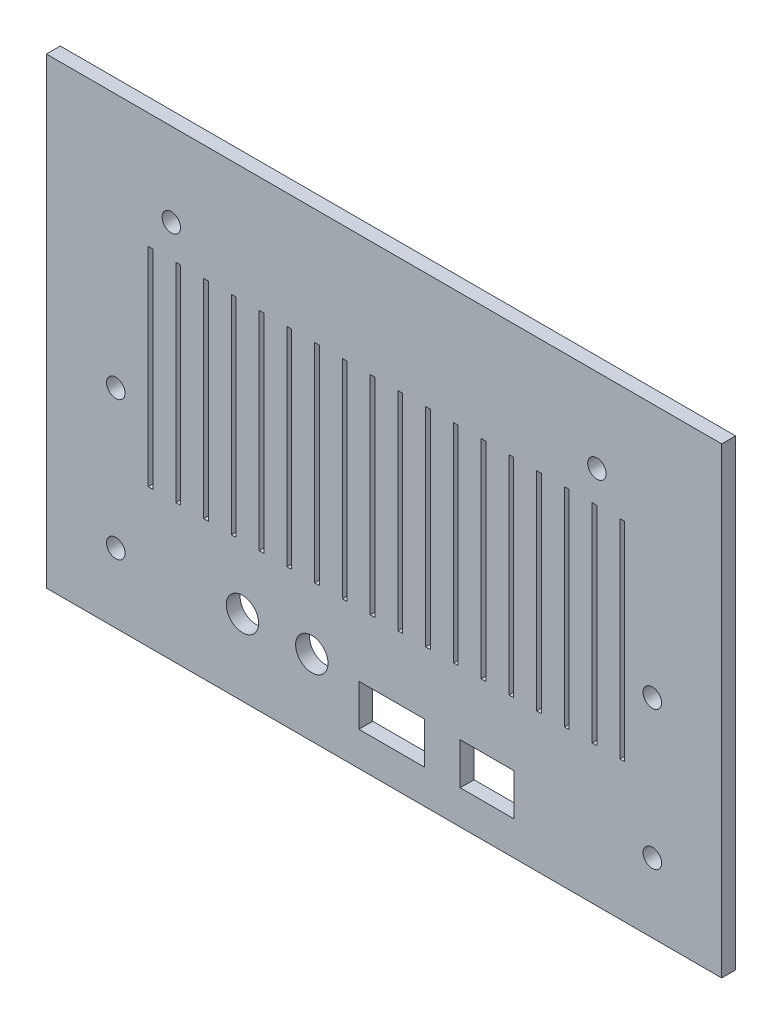
SolidWorks part; units mm, degrees
ref_plane "Front Plane" through (0, 0, 0) normal (0, 0, 1) x (1, 0, 0)
ref_plane "Top Plane" through (0, 0, 0) normal (0, 1, 0) x (1, 0, 0)
ref_plane "Right Plane" through (0, 0, 0) normal (1, 0, 0) x (0, 0, -1)
sketch "Sketch1" plane through (0, 0, 0) normal (0, 0, 1) x (1, 0, 0)
  line L1 (-48.2442, 79.6334) -> (97.7558, 79.6334)
  line L2 (-48.2442, 79.6334) -> (-48.2442, -20.3666)
  line L3 (-48.2442, -20.3666) -> (97.7558, -20.3666)
  line L4 (97.7558, 79.6334) -> (97.7558, -20.3666)
  dimension "D1" = 146
  dimension "D2" = 100
extrude "Boss-Extrude1" add sketch "Sketch1" along normal blind 3
sketch "Sketch2" plane through (0, 0, 3) normal (0, 0, 1) x (1, 0, 0)
  line L0 (-20.2442, 54.6334) -> (-19.2442, 54.6334)
  line L1 (-26.2442, 54.6334) -> (-25.2442, 54.6334)
  line L2 (-26.2442, 54.6334) -> (-26.2442, 9.6334)
  line L3 (-26.2442, 9.6334) -> (-25.2442, 9.6334)
  line L4 (-25.2442, 54.6334) -> (-25.2442, 9.6334)
  line L5 (-20.2442, 54.6334) -> (-20.2442, 9.6334)
  line L6 (-20.2442, 9.6334) -> (-19.2442, 9.6334)
  line L7 (-19.2442, 54.6334) -> (-19.2442, 9.6334)
  line L8 (-14.2442, 54.6334) -> (-13.2442, 54.6334)
  line L9 (-14.2442, 54.6334) -> (-14.2442, 9.6334)
  line L10 (-14.2442, 9.6334) -> (-13.2442, 9.6334)
  line L11 (-13.2442, 54.6334) -> (-13.2442, 9.6334)
  line L12 (-8.2442, 54.6334) -> (-7.2442, 54.6334)
  line L13 (-8.2442, 54.6334) -> (-8.2442, 9.6334)
  line L14 (-8.2442, 9.6334) -> (-7.2442, 9.6334)
  line L15 (-7.2442, 54.6334) -> (-7.2442, 9.6334)
  line L16 (-2.2442, 54.6334) -> (-1.2442, 54.6334)
  line L17 (-2.2442, 54.6334) -> (-2.2442, 9.6334)
  line L18 (-2.2442, 9.6334) -> (-1.2442, 9.6334)
  line L19 (-1.2442, 54.6334) -> (-1.2442, 9.6334)
  line L20 (3.7558, 54.6334) -> (4.7558, 54.6334)
  line L21 (3.7558, 54.6334) -> (3.7558, 9.6334)
  line L22 (3.7558, 9.6334) -> (4.7558, 9.6334)
  line L23 (4.7558, 54.6334) -> (4.7558, 9.6334)
  line L24 (-48.2442, 79.6334) -> (-48.2442, -20.3666) construction
  line L25 (-48.2442, -20.3666) -> (97.7558, -20.3666) construction
  line L26 (9.7558, 54.6334) -> (10.7558, 54.6334)
  line L27 (9.7558, 54.6334) -> (9.7558, 9.6334)
  line L28 (9.7558, 9.6334) -> (10.7558, 9.6334)
  line L29 (10.7558, 54.6334) -> (10.7558, 9.6334)
  line L30 (15.7558, 54.6334) -> (16.7558, 54.6334)
  line L31 (15.7558, 54.6334) -> (15.7558, 9.6334)
  line L32 (15.7558, 9.6334) -> (16.7558, 9.6334)
  line L33 (16.7558, 54.6334) -> (16.7558, 9.6334)
  line L34 (21.7558, 54.6334) -> (22.7558, 54.6334)
  line L35 (21.7558, 54.6334) -> (21.7558, 9.6334)
  line L36 (21.7558, 9.6334) -> (22.7558, 9.6334)
  line L37 (22.7558, 54.6334) -> (22.7558, 9.6334)
  line L38 (33.7558, 54.6334) -> (34.7558, 54.6334)
  line L39 (27.7558, 54.6334) -> (28.7558, 54.6334)
  line L40 (27.7558, 54.6334) -> (27.7558, 9.6334)
  line L41 (27.7558, 9.6334) -> (28.7558, 9.6334)
  line L42 (28.7558, 54.6334) -> (28.7558, 9.6334)
  line L43 (33.7558, 54.6334) -> (33.7558, 9.6334)
  line L44 (33.7558, 9.6334) -> (34.7558, 9.6334)
  line L45 (34.7558, 54.6334) -> (34.7558, 9.6334)
  line L46 (39.7558, 54.6334) -> (40.7558, 54.6334)
  line L47 (39.7558, 54.6334) -> (39.7558, 9.6334)
  line L48 (39.7558, 9.6334) -> (40.7558, 9.6334)
  line L49 (40.7558, 54.6334) -> (40.7558, 9.6334)
  line L50 (45.7558, 54.6334) -> (46.7558, 54.6334)
  line L51 (45.7558, 54.6334) -> (45.7558, 9.6334)
  line L52 (45.7558, 9.6334) -> (46.7558, 9.6334)
  line L53 (46.7558, 54.6334) -> (46.7558, 9.6334)
  line L54 (51.7558, 54.6334) -> (52.7558, 54.6334)
  line L55 (51.7558, 54.6334) -> (51.7558, 9.6334)
  line L56 (51.7558, 9.6334) -> (52.7558, 9.6334)
  line L57 (52.7558, 54.6334) -> (52.7558, 9.6334)
  line L58 (57.7558, 54.6334) -> (58.7558, 54.6334)
  line L59 (57.7558, 54.6334) -> (57.7558, 9.6334)
  line L60 (57.7558, 9.6334) -> (58.7558, 9.6334)
  line L61 (58.7558, 54.6334) -> (58.7558, 9.6334)
  line L62 (63.7558, 54.6334) -> (64.7558, 54.6334)
  line L63 (63.7558, 54.6334) -> (63.7558, 9.6334)
  line L64 (63.7558, 9.6334) -> (64.7558, 9.6334)
  line L65 (64.7558, 54.6334) -> (64.7558, 9.6334)
  line L66 (69.7558, 54.6334) -> (70.7558, 54.6334)
  line L67 (69.7558, 54.6334) -> (69.7558, 9.6334)
  line L68 (69.7558, 9.6334) -> (70.7558, 9.6334)
  line L69 (70.7558, 54.6334) -> (70.7558, 9.6334)
  line L70 (75.7558, 54.6334) -> (76.7558, 54.6334)
  line L71 (75.7558, 54.6334) -> (75.7558, 9.6334)
  line L72 (75.7558, 9.6334) -> (76.7558, 9.6334)
  line L73 (76.7558, 54.6334) -> (76.7558, 9.6334)
  line L74 (97.7558, -20.3666) -> (97.7558, 79.6334) construction
  dimension "D1" = 1
  dimension "D2" = 45
  dimension "D3" = 45
  dimension "D4" = 45
  dimension "D5" = 45
  dimension "D6" = 45
  dimension "D7" = 5
  dimension "D8" = 5
  dimension "D9" = 5
  dimension "D10" = 5
  dimension "D11" = 0
  dimension "D12" = 0
  dimension "D13" = 0
  dimension "D14" = 0
  dimension "D15" = 45
  dimension "D16" = 5
  dimension "D17" = 0
  dimension "D18" = 22
  dimension "D19" = 30
  dimension "D20" = 1
  dimension "D21" = 1
  dimension "D22" = 1
  dimension "D23" = 1
  dimension "D24" = 1
  dimension "D25" = 1
  dimension "D26" = 45
  dimension "D27" = 1
  dimension "D28" = 45
  dimension "D29" = 1
  dimension "D30" = 45
  dimension "D31" = 5
  dimension "D32" = 5
  dimension "D33" = 5
  dimension "D34" = 0
  dimension "D35" = 0
  dimension "D36" = 0
  dimension "D37" = 1
  dimension "D38" = 45
  dimension "D39" = 45
  dimension "D40" = 45
  dimension "D41" = 45
  dimension "D42" = 45
  dimension "D43" = 5
  dimension "D44" = 5
  dimension "D45" = 0
  dimension "D46" = 0
  dimension "D47" = 0
  dimension "D48" = 0
  dimension "D49" = 45
  dimension "D50" = 5
  dimension "D51" = 0
  dimension "D52" = 1
  dimension "D53" = 1
  dimension "D54" = 1
  dimension "D55" = 1
  dimension "D56" = 1
  dimension "D57" = 1
  dimension "D58" = 45
  dimension "D59" = 45
  dimension "D60" = 5
  dimension "D61" = 0
  dimension "D62" = 0
  dimension "D63" = 0
  dimension "D64" = 0
  dimension "D65" = 5
  dimension "D66" = 5
  dimension "D67" = 5
  dimension "D68" = 5
  dimension "D69" = 5
  dimension "D70" = 1
  dimension "D71" = 1
  dimension "D72" = 21
extrude "Cut-Extrude1" cut sketch "Sketch2" against normal through all
sketch "Sketch3" plane through (0, 0, 3) normal (0, 0, 1) x (1, 0, 0)
  circle A0 centre (-33.2442, -5.3666) radius 2
  circle A1 centre (82.7558, -5.3666) radius 2
  dimension "D1" = 4
  dimension "D2" = 4
extrude "Cut-Extrude2" cut sketch "Sketch3" against normal through all
sketch "Sketch4" plane through (0, 0, 0) normal (0, 0, -1) x (-1, 0, 0)
  line L0 (-50.8358, -6.0213) -> (-43.2158, -6.0213) construction
  line L1 (-52.8358, -13.0213) -> (-41.2158, -13.0213)
  line L2 (-52.8358, -13.0213) -> (-52.8358, -4.0213)
  line L3 (-52.8358, -4.0213) -> (-41.2158, -4.0213)
  line L4 (-41.2158, -13.0213) -> (-41.2158, -4.0213)
  line L5 (-50.8358, -11.0213) -> (-43.2158, -11.0213) construction
  line L6 (-50.8358, -11.0213) -> (-50.8358, -6.0213) construction
  line L7 (-43.2158, -11.0213) -> (-43.2158, -6.0213) construction
  dimension "D1" = 2
  dimension "D2" = 2
  dimension "D3" = 2
  dimension "D4" = 2
extrude "Cut-Extrude3" cut sketch "Sketch4" against normal through all
sketch "Sketch5" plane through (0, 0, 3) normal (0, 0, 1) x (1, 0, 0)
  line L0 (21.3058, -6.0213) -> (31.4658, -6.0213) construction
  line L1 (19.3058, -4.0213) -> (33.4658, -4.0213)
  line L2 (19.3058, -4.0213) -> (19.3058, -13.0213)
  line L3 (19.3058, -13.0213) -> (33.4658, -13.0213)
  line L4 (33.4658, -4.0213) -> (33.4658, -13.0213)
  line L5 (21.3058, -6.0213) -> (21.3058, -11.0213) construction
  line L6 (31.4658, -6.0213) -> (31.4658, -11.0213) construction
  line L7 (21.3058, -11.0213) -> (31.4658, -11.0213) construction
  dimension "D1" = 2
  dimension "D2" = 2
  dimension "D3" = 2
  dimension "D4" = 2
extrude "Cut-Extrude4" cut sketch "Sketch5" against normal through all
sketch "Sketch6" plane through (0, 0, 0) normal (0, 0, -1) x (-1, 0, 0)
  line L1 (-33.4658, -4.0213) -> (-19.3058, -4.0213) construction
  circle A0 centre (-9.1392, -4.0213) radius 3.5
  circle A1 centre (5.8608, -4.0213) radius 3.5
  dimension "D2" = 7
  dimension "D1" = 7
  dimension "D3" = 0
  dimension "D4" = 0
  dimension "D5" = 15
extrude "Cut-Extrude5" cut sketch "Sketch6" against normal through all
sketch "Sketch8" plane through (0, 0, 3) normal (0, 0, 1) x (1, 0, 0)
  circle A0 centre (82.7558, 24.6334) radius 2
  circle A1 centre (-33.2442, 24.6334) radius 2
  dimension "D1" = 4
extrude "Cut-Extrude6" cut sketch "Sketch8" against normal through all
sketch "Sketch9" plane through (0, 0, 3) normal (0, 0, 1) x (1, 0, 0)
  circle A0 centre (-21.2442, 61.6334) radius 2
  circle A1 centre (70.7731, 61.5321) radius 2
  dimension "D1" = 4
  dimension "D2" = 4
extrude "Cut-Extrude7" cut sketch "Sketch9" against normal through all
